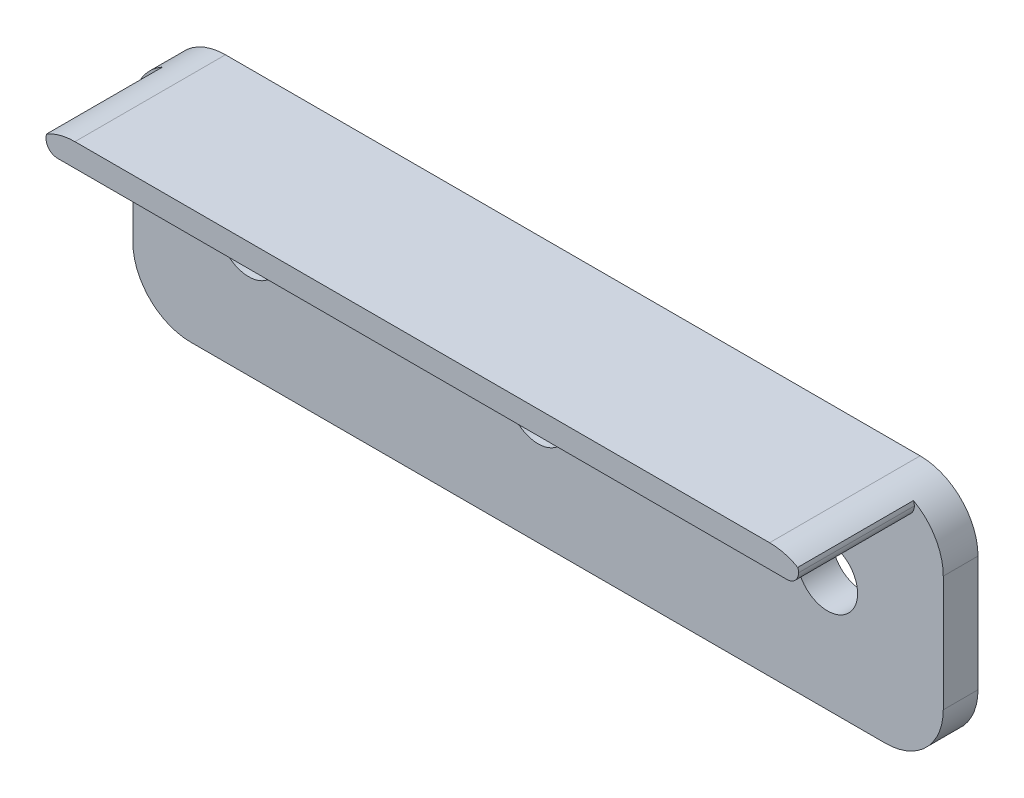
SolidWorks part; units mm, degrees
ref_plane "正面" through (0, 0, 0) normal (0, 0, 1) x (1, 0, 0)
ref_plane "平面" through (0, 0, 0) normal (0, 1, 0) x (1, 0, 0)
ref_plane "右側面" through (0, 0, 0) normal (1, 0, 0) x (0, 0, -1)
sketch "ｽｹｯﾁ2" plane through (0, 0, 0) normal (0, 0, 1) x (1, 0, 0)
  line L0 (-25, 0) -> (25, 0) construction
  line L2 (-35, -10) -> (35, -10)
  line L3 (-35, -10) -> (-35, 10)
  line L4 (-35, 10) -> (35, 10)
  line L5 (35, -10) -> (35, 10)
  line L6 (-35, -10) -> (35, 10) construction
  line L7 (-35, 10) -> (35, -10) construction
  circle A0 centre (-25, 0) radius 2.6
  circle A1 centre (25, 0) radius 2.6
  circle A2 centre (0, 0) radius 2.6
  point P4 (0, 0)
  point P7 (0, 0)
  dimension "D1" = 5.2
  dimension "D4" = 10
  dimension "D2" = 50
  dimension "D3" = 20
extrude "ﾎﾞｽ - 押し出し1" add sketch "ｽｹｯﾁ2" along normal blind 3
sketch "ｽｹｯﾁ3" plane through (0, 0, 3) normal (0, 0, 1) x (1, 0, 0)
  line L0 (0, -10) -> (0, 10) construction
  line L1 (-35, -10) -> (35, -10) construction
  line L2 (35, 10) -> (-35, 10) construction
  line L4 (32.5, 8) -> (-32.5, 8)
  line L5 (32.5, 8) -> (32.5, 10)
  line L6 (32.5, 10) -> (-32.5, 10)
  line L7 (-32.5, 8) -> (-32.5, 10)
  line L8 (32.5, 8) -> (-32.5, 10) construction
  line L9 (32.5, 10) -> (-32.5, 8) construction
  point P6 (0, 9)
  dimension "D1" = 2
  dimension "D2" = 65
extrude "ﾎﾞｽ - 押し出し2" add sketch "ｽｹｯﾁ3" along normal blind 10
fillet "ﾌｨﾚｯﾄ1" radius 1 4 edges at (-32.5, 10, 8) (-32.5, 8, 8) (32.5, 10, 8) (32.5, 8, 8)
fillet "ﾌｨﾚｯﾄ2" radius 5 4 edges at (-35, -10, 1.5) (-35, 10, 1.5) (35, -10, 1.5) (35, 10, 1.5)
